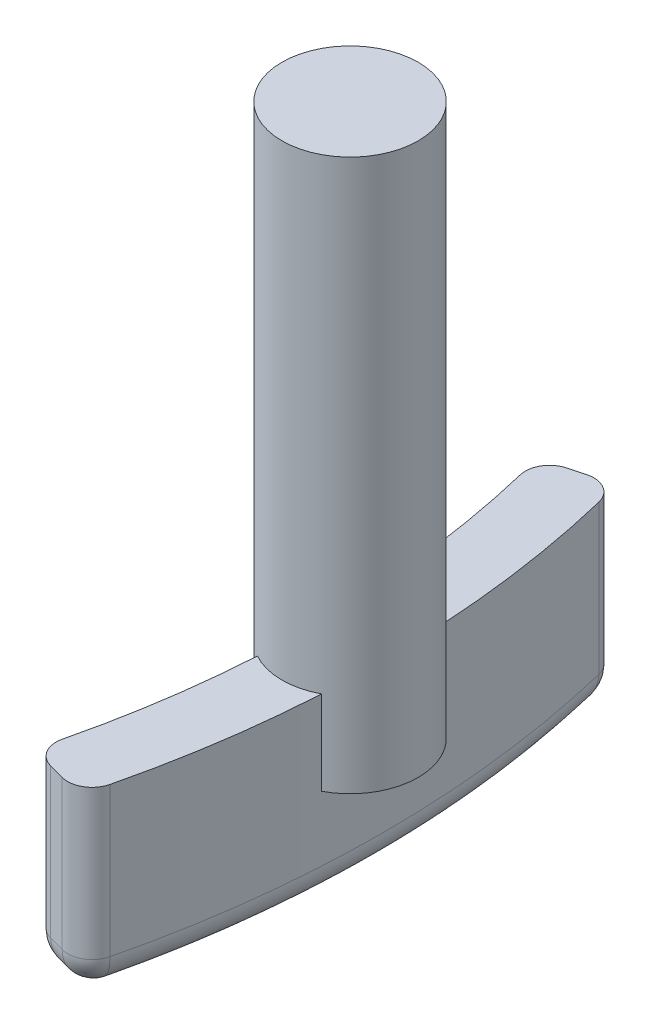
SolidWorks part; units mm, degrees
material "ABS"
ref_plane "Front Plane" through (0, 0, 0) normal (0, 0, 1) x (1, 0, 0)
ref_plane "Top Plane" through (0, 0, 0) normal (0, 1, 0) x (1, 0, 0)
ref_plane "Right Plane" through (0, 0, 0) normal (1, 0, 0) x (0, 0, -1)
sketch "Эскиз1" plane through (0, 0, 0) normal (0, 1, 0) x (1, 0, 0)
  line L14 (-0.842, -7.9563) -> (-0.3589, -8.0858)
  line L15 (-0.842, 7.9563) -> (-0.3589, 8.0858)
  arc A42 (-0.3589, -8.0858) -> (0.5641, -7.538) centre (-0.1648, -7.3613) ccw
  arc A43 (0.5641, 7.538) -> (0.5641, -7.538) centre (-30.5354, 0) cw
  arc A44 (0.5641, 7.538) -> (-0.3589, 8.0858) centre (-0.1648, 7.3613) ccw
  arc A45 (-0.842, 7.9563) -> (-1.3768, 7.0555) centre (-0.6479, 7.2319) ccw
  arc A46 (-1.3768, 7.0555) -> (-1.3768, -7.0555) centre (-30.5354, 0) cw
  arc A47 (-0.842, -7.9563) -> (-1.3768, -7.0555) centre (-0.6479, -7.2319) cw
extrude "Бобышка-Вытянуть1" add sketch "Эскиз1" along normal blind 5.6
ref_plane "Плоскость1" through (0, 3, 0) normal (0, 1, 0) x (1, 0, 0)
sketch "Эскиз2" plane through (0, 3, 0) normal (0, 1, 0) x (1, 0, 0)
  circle A2 centre (0.4313, 0) radius 2.1
  dimension "D1" = 4.2
extrude "Бобышка-Вытянуть2" add sketch "Эскиз2" along normal blind 17
fillet "Скругление1" radius 1 8 edges at (-1.2928, 0, -7.6148) (-0.6004, 0, -8.021) (0.218, 0, -8.0063) (1.4646, 0, 0) (0.218, 0, 8.0063) (-0.6004, 0, 8.021) (-1.2928, 0, 7.6148) (-0.5354, 0, 0)
